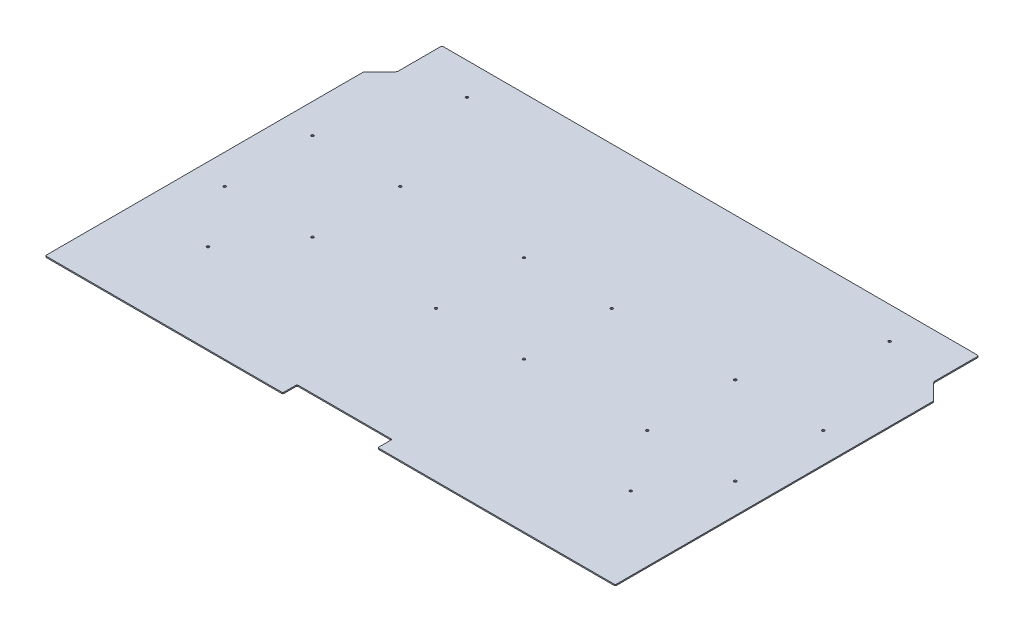
SolidWorks part; units mm, degrees
material "PE High Density"
ref_plane "Front Plane" through (0, 0, 0) normal (0, 0, 1) x (1, 0, 0)
ref_plane "Top Plane" through (0, 0, 0) normal (0, 1, 0) x (1, 0, 0)
ref_plane "Right Plane" through (0, 0, 0) normal (1, 0, 0) x (0, 0, -1)
sketch "Sketch1" plane through (0, 0, 0) normal (0, 1, 0) x (1, 0, 0)
  line L0 (-717.55, 504.825) -> (-717.55, 392.6105)
  line L1 (-758.825, -508) -> (758.825, -508)
  line L2 (-762, -504.825) -> (-762, 341.5849)
  line L3 (-714.375, 508) -> (714.375, 508)
  line L4 (762, -504.825) -> (762, 341.5849)
  line L5 (-762, -508) -> (762, 508) construction
  line L6 (-762, 508) -> (762, -508) construction
  line L8 (717.55, 504.825) -> (717.55, 392.6105)
  line L10 (-761.0701, 343.8299) -> (-721.2697, 383.6303)
  line L11 (761.0701, 343.8299) -> (721.2697, 383.6303)
  arc A2 (717.55, 392.6105) -> (721.2697, 383.6303) centre (730.25, 392.6105) ccw
  arc A3 (-721.2697, 383.6303) -> (-717.55, 392.6105) centre (-730.25, 392.6105) ccw
  arc A4 (761.0701, 343.8299) -> (762, 341.5849) centre (758.825, 341.5849) cw
  arc A5 (717.55, 504.825) -> (714.375, 508) centre (714.375, 504.825) ccw
  arc A6 (758.825, -508) -> (762, -504.825) centre (758.825, -504.825) ccw
  arc A7 (-758.825, -508) -> (-762, -504.825) centre (-758.825, -504.825) cw
  arc A8 (-761.0701, 343.8299) -> (-762, 341.5849) centre (-758.825, 341.5849) ccw
  arc A9 (-717.55, 504.825) -> (-714.375, 508) centre (-714.375, 504.825) cw
  point P0 (0, 0)
  point P18 (762, 342.9)
  point P21 (717.55, 508)
  point P30 (-762, 342.9)
  point P33 (-717.55, 508)
  dimension "D5" = 44.45
  dimension "D6" = 12.7
  dimension "D7" = 3.175
  dimension "D1" = 1524
  dimension "D2" = 1016
  dimension "D3" = 165.1
  dimension "D4" = 135
extrude "Boss-Extrude1" add sketch "Sketch1" along normal blind 3.175
sketch "Sketch2" plane through (0, 3.175, 0) normal (0, 1, 0) x (1, 0, 0)
  line L0 (-565.15, 9.525) -> (565.15, 9.525) construction
  line L1 (565.15, -269.875) -> (-565.15, -269.875) construction
  line L2 (565.15, -269.875) -> (565.15, 422.275) construction
  line L3 (565.15, 422.275) -> (-565.15, 422.275) construction
  line L4 (-565.15, -269.875) -> (-565.15, 422.275) construction
  line L5 (565.15, -269.875) -> (-565.15, 422.275) construction
  line L6 (565.15, 422.275) -> (-565.15, -269.875) construction
  line L7 (-447.675, -107.95) -> (-682.625, -107.95) construction
  line L8 (-447.675, -107.95) -> (-447.675, 127) construction
  line L9 (-447.675, 127) -> (-682.625, 127) construction
  line L10 (-682.625, -107.95) -> (-682.625, 127) construction
  line L11 (-447.675, -107.95) -> (-682.625, 127) construction
  line L12 (-447.675, 127) -> (-682.625, -107.95) construction
  line L13 (682.625, -107.95) -> (447.675, -107.95) construction
  line L14 (682.625, -107.95) -> (682.625, 127) construction
  line L15 (682.625, 127) -> (447.675, 127) construction
  line L16 (447.675, -107.95) -> (447.675, 127) construction
  line L17 (682.625, -107.95) -> (447.675, 127) construction
  line L18 (682.625, 127) -> (447.675, -107.95) construction
  line L20 (-117.475, -107.95) -> (117.475, -107.95) construction
  line L21 (-117.475, -107.95) -> (-117.475, 127) construction
  line L22 (-117.475, 127) -> (117.475, 127) construction
  line L23 (117.475, -107.95) -> (117.475, 127) construction
  line L24 (-117.475, -107.95) -> (117.475, 127) construction
  line L25 (-117.475, 127) -> (117.475, -107.95) construction
  point P0 (0, 0)
  point P5 (0, 9.525)
  point P6 (-565.15, 9.525)
  point P8 (0, 76.2)
  point P13 (565.15, 9.525)
  dimension "D1" = 1130.3
  dimension "D2" = 692.15
  dimension "D3" = 76.2
  dimension "D4" = 234.95
  dimension "D5" = 127
hole_wizard "17/64 (0.26563) Diameter Hole1" positions "Sketch3" profile "Sketch4" hole size "17/64" standard "ANSI Inch" end condition through all
sketch "Sketch3" plane through (0, 3.175, 0) normal (0, 1, 0) x (1, 0, 0)
  point P0 (-565.15, 422.275)
  point P3 (565.15, 422.275)
  point P6 (565.15, -269.875)
  point P9 (-565.15, -269.875)
  point P47 (-682.625, 127)
  point P50 (-447.675, 127)
  point P53 (-682.625, -107.95)
  point P56 (-447.675, -107.95)
  point P59 (-117.475, 127)
  point P62 (117.475, 127)
  point P65 (-117.475, -107.95)
  point P68 (117.475, -107.95)
  point P71 (447.675, 127)
  point P74 (682.625, 127)
  point P77 (447.675, -107.95)
  point P80 (682.625, -107.95)
sketch "Sketch4" plane through (-565.15, 3.175, -422.275) normal (1, 0, 0) x (0, 0, 1)
  line L0 (0, 0) -> (0, 3.175)
  line L1 (0, 3.175) -> (3.3735, 3.175)
  line L2 (3.3735, 3.175) -> (3.3735, 0)
  line L5 (3.3735, 0) -> (0, 0)
  line L11 (0, -6.35) -> (0, 107.95) construction
  dimension "Thru Hole Dia." = 6.747
  dimension "Thru Hole Depth" = 3.175
sketch "Sketch5" plane through (0, 3.175, 0) normal (0, 1, 0) x (1, 0, 0)
  line L0 (-758.825, -508) -> (758.825, -508) construction
  line L1 (-127, -508) -> (127, -508)
  line L2 (-127, -508) -> (-127, -469.9)
  line L3 (-127, -469.9) -> (127, -469.9)
  line L4 (127, -508) -> (127, -469.9)
  line L5 (-762, 341.5849) -> (-762, -504.825) construction
  dimension "D1" = 254
  dimension "D2" = 38.1
  dimension "D3" = 635
extrude "Cut-Extrude1" cut sketch "Sketch5" against normal through all
fillet "Fillet1" radius 3.175 4 edges at (127, 1.5875, 508) (127, 1.5875, 469.9) (-127, 1.5875, 469.9) (-127, 1.5875, 508)
